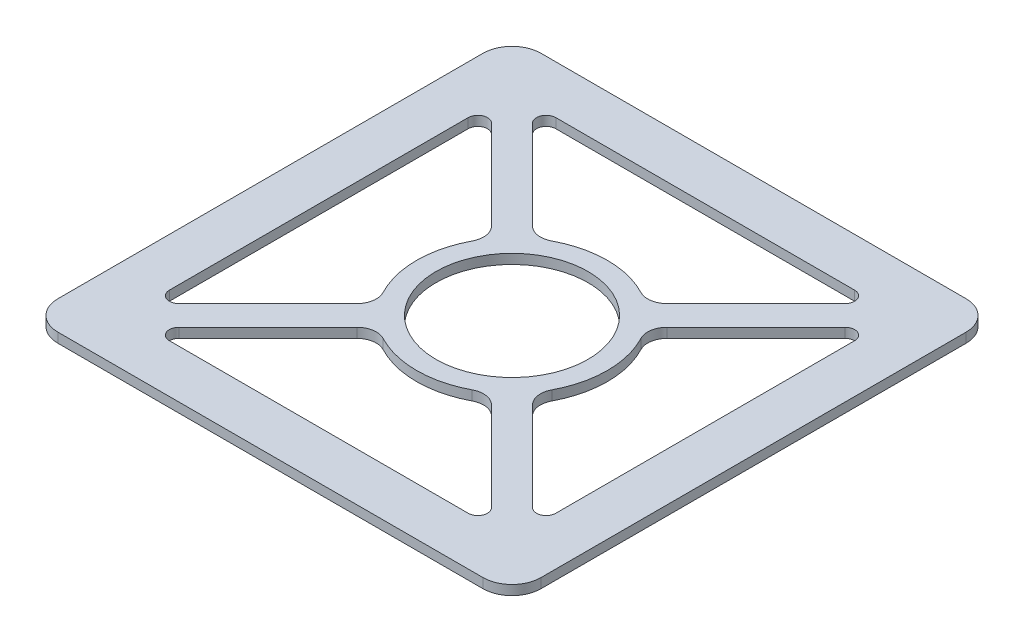
SolidWorks part; units mm, degrees
ref_plane "Front Plane" through (0, 0, 0) normal (0, 0, 1) x (1, 0, 0)
ref_plane "Top Plane" through (0, 0, 0) normal (0, 1, 0) x (1, 0, 0)
ref_plane "Right Plane" through (0, 0, 0) normal (1, 0, 0) x (0, 0, -1)
sketch "Sketch1" plane through (0, 0, 0) normal (0, 1, 0) x (1, 0, 0)
  line L0 (20, 17.8787) -> (20, -17.8787)
  line L1 (-25, -25) -> (25, -25)
  line L2 (-25, -25) -> (-25, 25)
  line L3 (-25, 25) -> (25, 25)
  line L4 (25, -25) -> (25, 25)
  line L5 (-25, -25) -> (25, 25) construction
  line L6 (-25, 25) -> (25, -25) construction
  line L7 (17.8787, -20) -> (-17.8787, -20)
  line L8 (-20, -17.8787) -> (-20, 17.8787)
  line L9 (-17.8787, 20) -> (17.8787, 20)
  line L10 (20, 17.8787) -> (7.9623, 5.841)
  line L11 (17.8787, 20) -> (5.841, 7.9623)
  line L12 (-17.8787, 20) -> (-5.841, 7.9623)
  line L13 (-20, 17.8787) -> (-7.9623, 5.841)
  line L14 (-20, -17.8787) -> (-7.9623, -5.841)
  line L15 (-17.8787, -20) -> (-5.841, -7.9623)
  line L16 (17.8787, -20) -> (5.841, -7.9623)
  line L17 (20, -17.8787) -> (7.9623, -5.841)
  circle A0 centre (0, 0) radius 7.875
  arc A1 (5.841, 7.9623) -> (-5.841, 7.9623) centre (0, 0) ccw
  circle A2 centre (0, 0) radius 9.875 construction
  arc A3 (-7.9623, 5.841) -> (-7.9623, -5.841) centre (0, 0) ccw
  arc A4 (-5.841, -7.9623) -> (5.841, -7.9623) centre (0, 0) ccw
  arc A5 (7.9623, -5.841) -> (7.9623, 5.841) centre (0, 0) ccw
  point P0 (0, 0)
  dimension "D1" = 15.75
  dimension "D3" = 50
  dimension "D4" = 50
  dimension "D5" = 5
  dimension "D6" = 1.5
  dimension "D7" = 1.5
  dimension "D8" = 1.5
  dimension "D9" = 1.5
  dimension "D10" = 1.5
  dimension "D11" = 1.5
  dimension "D12" = 1.5
  dimension "D13" = 1.5
  dimension "D2" = 2
base flange "Base-Flange1" sketch "Sketch1" thickness 1 reverse thickness direction no parameters "D1"=0.6
fillet "Fillet1" radius 3 4 edges at (25, -0.5, 25) (25, -0.5, -25) (-25, -0.5, -25) (-25, -0.5, 25)
fillet "Fillet2" radius 1 8 edges at (17.8787, -0.5, 20) (20, -0.5, 17.8787) (20, -0.5, -17.8787) (17.8787, -0.5, -20) (-17.8787, -0.5, 20) (-20, -0.5, 17.8787) (-17.8787, -0.5, -20) (-20, -0.5, -17.8787)
fillet "Fillet3" radius 2 8 edges at (5.841, -0.5, 7.9623) (-5.841, -0.5, 7.9623) (-5.841, -0.5, -7.9623) (7.9623, -0.5, 5.841) (7.9623, -0.5, -5.841) (5.841, -0.5, -7.9623) (-7.9623, -0.5, -5.841) (-7.9623, -0.5, 5.841)
sketch "Bend-Lines1" plane through (0, 0, 0) normal (0, 1, 0) x (1, 0, 0)
sketch "Bounding-Box1" plane through (0, 0, 0) normal (0, 1, 0) x (1, 0, 0)
sheet metal parameters "Sheet-Metal(1)" thickness 1 parameters "D1"=0.6
flat pattern "Flat-Pattern(1)" [suppressed]
sketch "Bend-Lines2" plane through (0, 0, 0) normal (0, 1, 0) x (1, 0, 0)
sketch "Bounding-Box2" [suppressed] plane through (0, 0, 0) normal (0, 1, 0) x (1, 0, 0)
